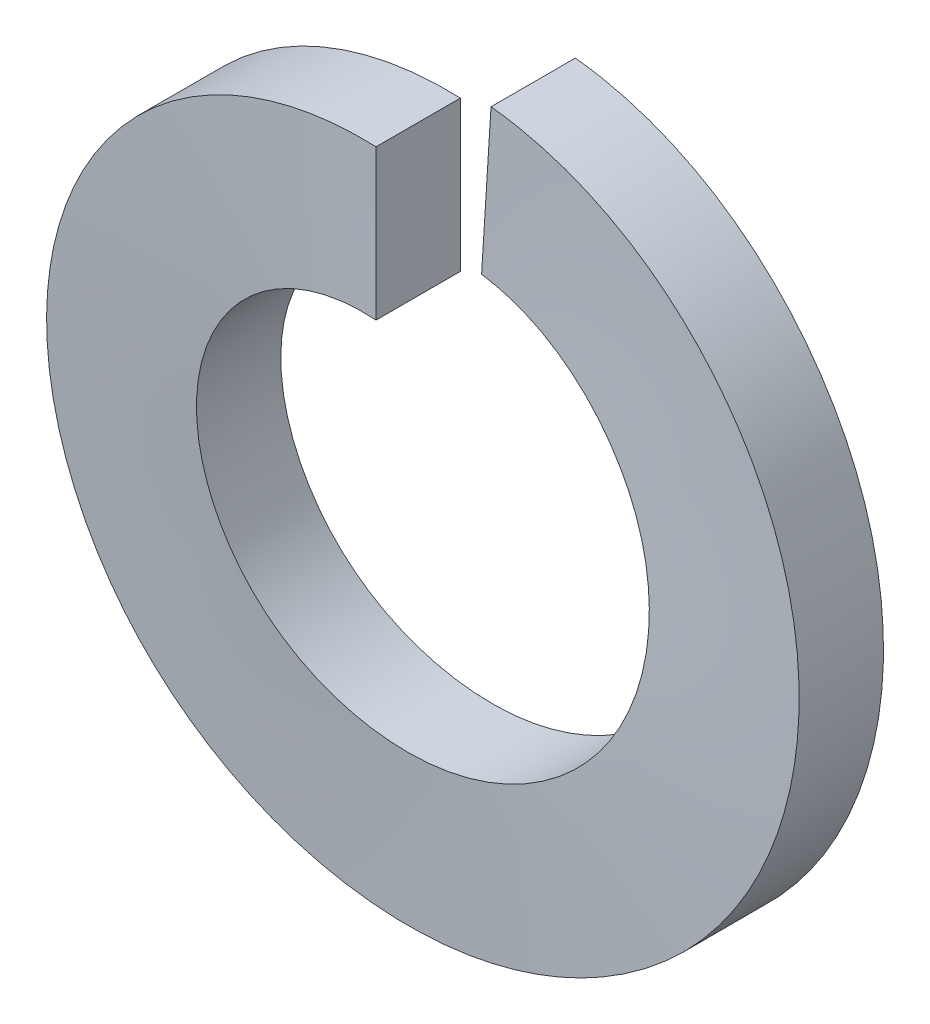
SolidWorks part; units mm, degrees
ref_plane "Front Plane" through (0, 0, 0) normal (0, 0, 1) x (1, 0, 0)
ref_plane "Top Plane" through (0, 0, 0) normal (0, 1, 0) x (1, 0, 0)
ref_plane "Right Plane" through (0, 0, 0) normal (1, 0, 0) x (0, 0, -1)
sketch "Sketch1" plane through (0, 0, 0) normal (0, 0, 1) x (1, 0, 0)
  line L0 (0, 2.6543) -> (0, 1.524) construction
  circle A0 centre (0, 0) radius 2.6543
  circle A1 centre (0, 0) radius 1.524 construction
  dimension "ID" = 3.048
  dimension "OD" = 5.3086
curve "Helix/Spiral1" pitch 0.7056 height 0.6985 radius 2.6543 left hand yes centre (0, 0, 0) axis (0, 0, -1) start towards (0, 1, 0) parameters "HT"=0.6985
sketch "Sketch2" plane through (0, 0, 0) normal (1, 0, 0) x (0, 0, -1)
  line L1 (0, 2.6543) -> (-0.635, 2.6543)
  line L2 (0, 2.6543) -> (0, 1.524)
  line L3 (0, 1.524) -> (-0.635, 1.524)
  line L4 (-0.635, 2.6543) -> (-0.635, 1.524)
  dimension "THK" = 0.635
sweep "Sweep1" add profiles "Sketch2" path "Helix/Spiral1"
equation "\"HT@Helix/Spiral1\" = \"THK@Sketch2\"*1.1"
